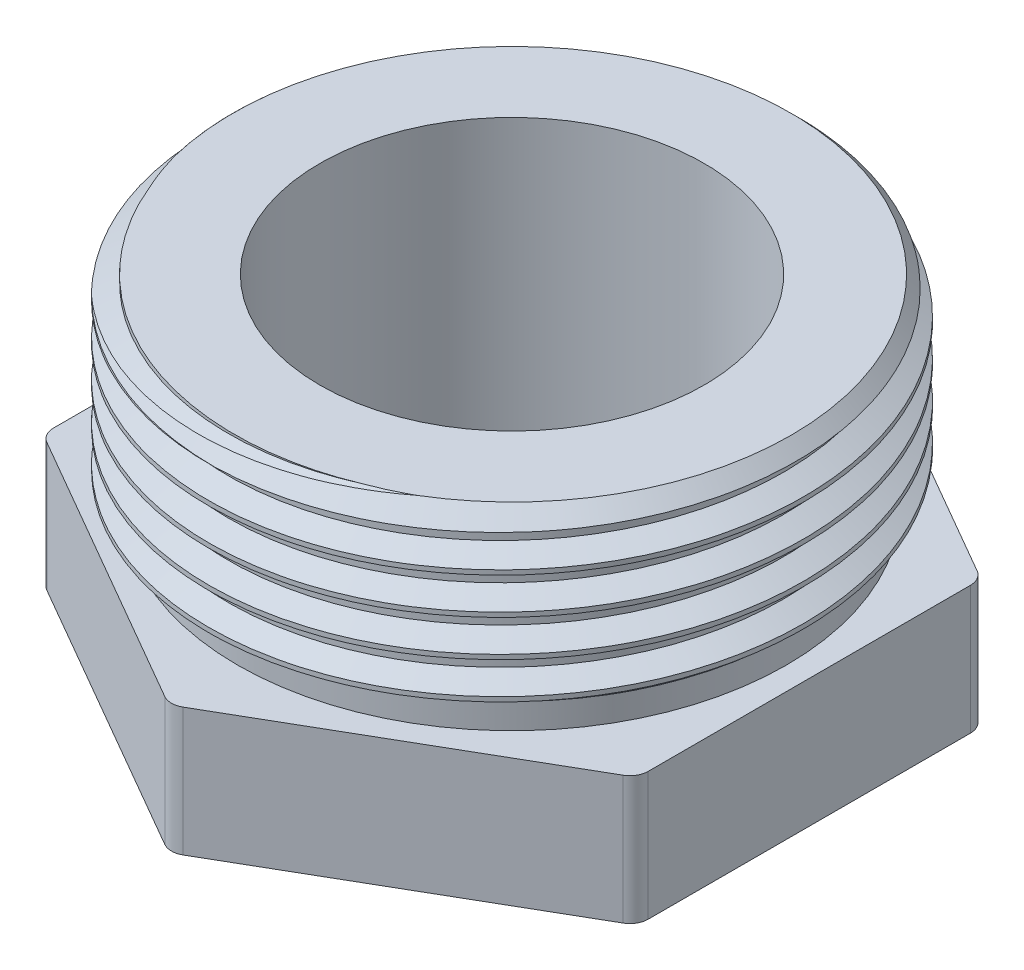
SolidWorks part; units mm, degrees
ref_plane "Front Plane" through (0, 0, 0) normal (0, 0, 1) x (1, 0, 0)
ref_plane "Top Plane" through (0, 0, 0) normal (0, 1, 0) x (1, 0, 0)
ref_plane "Right Plane" through (0, 0, 0) normal (1, 0, 0) x (0, 0, -1)
sketch "Sketch1" plane through (0, 0, 0) normal (0, 1, 0) x (1, 0, 0)
  line L1 (0, 37.5278) -> (-32.5, 18.7639)
  line L2 (-32.5, 18.7639) -> (-32.5, -18.7639)
  line L3 (-32.5, -18.7639) -> (0, -37.5278)
  line L4 (0, -37.5278) -> (32.5, -18.7639)
  line L5 (32.5, -18.7639) -> (32.5, 18.7639)
  line L6 (32.5, 18.7639) -> (0, 37.5278)
  circle A0 centre (0, 0) radius 32.5 construction
  circle A1 centre (0, 0) radius 21
  dimension "D2" = 42
  dimension "D1" = 65
extrude "Boss-Extrude1" add sketch "Sketch1" along normal blind 14
sketch "Sketch2" plane through (0, 14, 0) normal (0, 1, 0) x (1, 0, 0)
  circle A0 centre (0, 0) radius 30
  circle A1 centre (0, 0) radius 21 construction
  circle A2 centre (0, 0) radius 21
  dimension "D1" = 60
extrude "Boss-Extrude2" add sketch "Sketch2" along normal blind 3
sketch "Sketch3" plane through (0, 17, 0) normal (0, 1, 0) x (1, 0, 0)
  circle A1 centre (0, 0) radius 32.5
  circle A3 centre (0, 0) radius 21 construction
  circle A4 centre (0, 0) radius 21
  dimension "D1" = 65
extrude "Boss-Extrude3" add sketch "Sketch3" along normal blind 19
chamfer "Chamfer1" distance 2 angle 45 1 edges at (0, 36, 32.5)
thread "Thread1" pitch 4 method cut trim with start face yes trim with end face yes profile "Thread Profile1" start angle 0, offset 11, length 0, pitch 4, diameter 65
ref_plane "Plane1" through (-32.5, 45, 0) normal (0, 0, 1) x (-1, 0, 0)
sketch "Thread Profile1" plane through (-32.5, 45, 0) normal (0, 0, 1) x (-1, 0, 0)
  line L0 (0, 0) -> (0, 4) construction
  line L11 (0, 0) -> (0, 3.5)
  line L12 (0, 3.5) -> (-2.1651, 2.25)
  line L13 (-2.1651, 2.25) -> (-2.1651, 1.25)
  line L15 (-2.1651, 1.25) -> (0, 0)
  line L17 (-2.1651, 1.75) -> (0, 1.75) construction
  point P2 (0, 0)
  dimension "Pitch" = 4
  dimension "Profile_Angle" = 60
  dimension "Profile_Land" = 1
  dimension "Profile_Height" = 2.1651
fillet "Fillet1" radius 2 6 edges at (0, 7, 37.5278) (-32.5, 7, 18.7639) (-32.5, 7, -18.7639) (0, 7, -37.5278) (32.5, 7, 18.7639) (32.5, 7, -18.7639)
